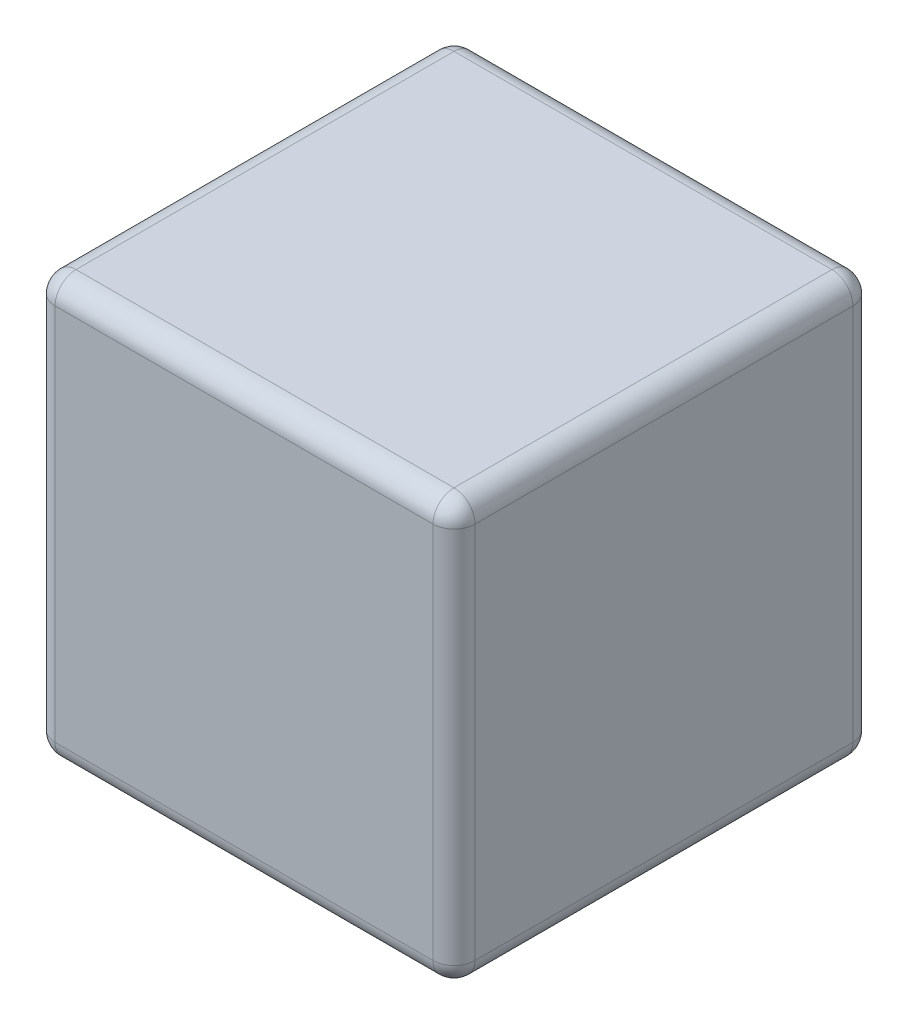
SolidWorks part; units mm, degrees
ref_plane "Front Plane" through (0, 0, 0) normal (0, 0, 1) x (1, 0, 0)
ref_plane "Top Plane" through (0, 0, 0) normal (0, 1, 0) x (1, 0, 0)
ref_plane "Right Plane" through (0, 0, 0) normal (1, 0, 0) x (0, 0, -1)
sketch "Sketch1" plane through (0, 0, 0) normal (0, 1, 0) x (1, 0, 0)
  line L1 (0, 0) -> (20, 0)
  line L2 (0, 0) -> (0, 20)
  line L3 (0, 20) -> (20, 20)
  line L4 (20, 0) -> (20, 20)
  dimension "D1" = 20
  dimension "D2" = 20
extrude "Boss-Extrude1" add sketch "Sketch1" along normal blind 20
fillet "Fillet1" radius 1 12 edges at (20, 10, -20) (20, 0, -10) (10, 0, 0) (0, 10, 0) (20, 10, 0) (20, 20, -10) (10, 20, 0) (0, 0, -10) (10, 0, -20) (0, 10, -20) (0, 20, -10) (10, 20, -20)
sketch3d "URDF Reference"
  line L0 (0, 0, 0) -> (10, 0, 0) construction
  line L1 (0, 0, 0) -> (0, 0, -10) construction
  point P0 (0, 0, 0)
  point P1 (0, 0, 0)
